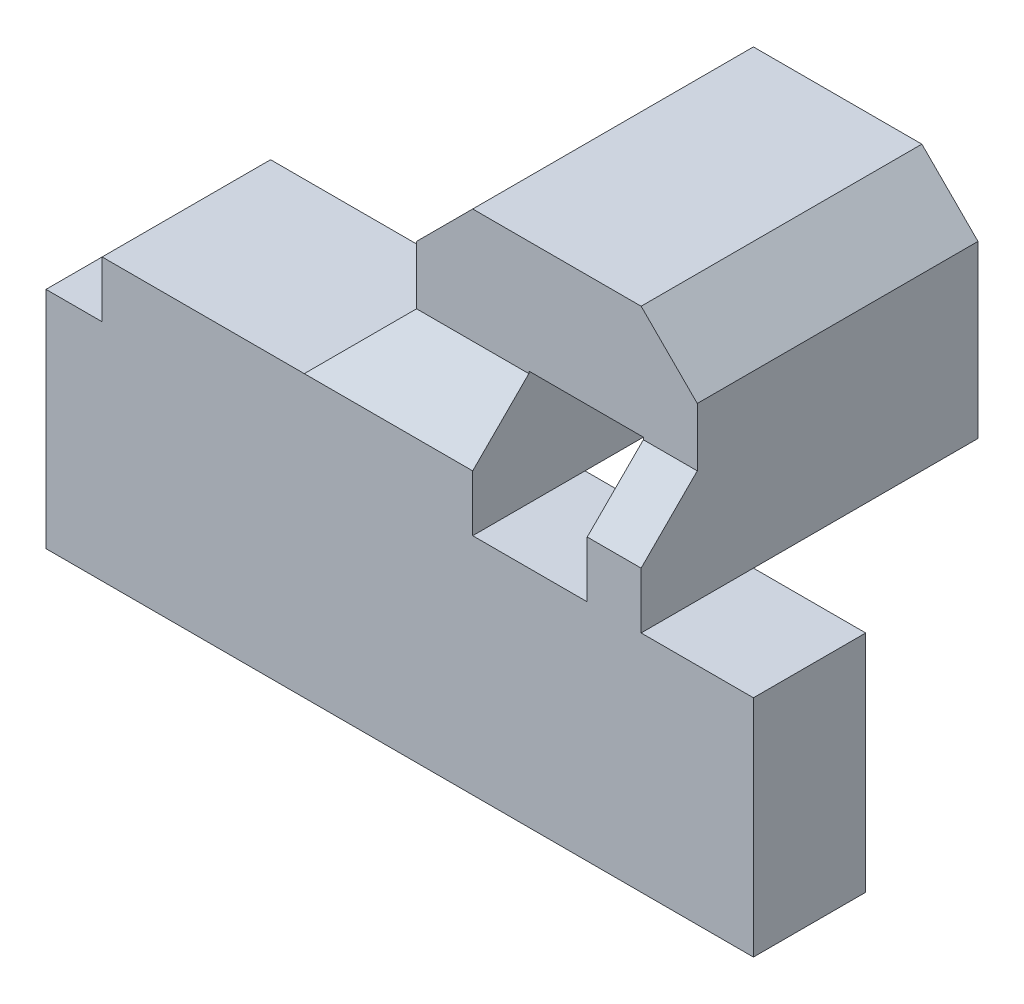
SolidWorks part; units mm, degrees
material "ABS"
ref_plane "Płaszczyzna przednia" through (0, 0, 0) normal (0, 0, 1) x (1, 0, 0)
ref_plane "Płaszczyzna górna" through (0, 0, 0) normal (0, 1, 0) x (1, 0, 0)
ref_plane "Płaszczyzna prawa" through (0, 0, 0) normal (1, 0, 0) x (0, 0, -1)
sketch "Szkic1" plane through (0, 0, 0) normal (0, 0, 1) x (1, 0, 0)
  line L1 (-29, -10) -> (29, -10)
  line L2 (-29, -10) -> (-29, 10)
  line L3 (-29, 10) -> (29, 10)
  line L4 (29, -10) -> (29, 10)
  line L5 (-29, -10) -> (29, 10) construction
  line L6 (-29, 10) -> (29, -10) construction
  point P0 (0, 0)
  dimension "D1" = 20
  dimension "D2" = 58
extrude "Dodanie-wyciągnięcie1" add sketch "Szkic1" along normal blind 5
sketch "Szkic2" plane through (29, 0, 0) normal (1, 0, 0) x (0, 0, -1)
  line L0 (0, 15) -> (-10, 15)
  line L1 (0, 10) -> (5, 10)
  line L2 (0, 10) -> (0, 15)
  line L3 (0, 15) -> (5, 15)
  line L4 (5, 10) -> (5, 15)
  line L5 (-5, 10) -> (0, 10)
  line L6 (-10, 15) -> (-10, 10)
  line L7 (-10, 10) -> (-5, 10)
  line M2 (0, 10) -> (-5, 10)
  dimension "D1" = 5
  dimension "D2" = 5
extrude "Dodanie-wyciągnięcie2" add sketch "Szkic2" against normal up to surface (58 mm away) contours L2 M2 | L1 L4 L3 L2 region at (29, 12.5, 5) region at (29, 12.5, -2.5) up to face at (-29, 0, 2.5)
sketch "Szkic3" plane through (0, -10, 0) normal (0, -1, 0) x (1, 0, 0)
  line L0 (-29, 0) -> (-34, 5)
  line L1 (-29, 5) -> (-29, 0) construction
  line L2 (-29, 0) -> (-34, 0) construction
  line L3 (-34, 5) -> (-34, 10)
  line L4 (-34, 10) -> (-29, 10)
  line L5 (-29, 10) -> (-24, 5)
  line L6 (-29, 5) -> (29, 5) construction
  line L7 (-29, 5) -> (29, 5)
  line L8 (-29, 5) -> (-29, 0)
  point P12 (0, 0)
  line M7 (29, 5) -> (-29, 5)
  line M8 (-29, 5) -> (-29, 0)
  dimension "D1" = 45
  dimension "D2" = 5
  dimension "D3" = 5
extrude "Dodanie-wyciągnięcie3" add sketch "Szkic3" against normal blind 20 contours L5 L4 L3 L0 M8 M7 region at (-30.25, -10, 6.25)
sketch "Szkic4" plane through (0, 0, 5) normal (0, 0, 1) x (1, 0, 0)
  line L1 (29, 10) -> (19, 10)
  line L2 (29, 10) -> (29, 15)
  line L3 (29, 15) -> (19, 15)
  line L4 (19, 10) -> (19, 15)
  line L6 (29, -10) -> (29, 10) construction
  line L7 (-29, 15) -> (29, 15) construction
  line L8 (29, 10) -> (-24, 10) construction
  point P4 (0, 0)
  point P8 (0, 0)
  dimension "D1" = 5
  dimension "D2" = 10
extrude "Wytnij-wyciągnięcie1" cut sketch "Szkic4" against normal through all and the other way through all
sketch "Szkic5" plane through (0, 0, 5) normal (0, 0, 1) x (1, 0, 0)
  line L0 (-34, 10) -> (-34, -10) construction
  line L1 (14.2, 10) -> (4, 10)
  line L2 (14.2, 10) -> (14.2, 20.2)
  line L3 (14.2, 20.2) -> (4, 20.2)
  line L4 (4, 10) -> (4, 20.2)
  line L5 (14.2, 10) -> (4, 20.2) construction
  line L6 (14.2, 20.2) -> (4, 10) construction
  line L7 (19, 10) -> (-24, 10) construction
  line L9 (29, 10) -> (19, 10) construction
  line L10 (-6, 10) -> (19, 10)
  line L11 (-6, 10) -> (-6, 30.2)
  line L12 (-6, 30.2) -> (19, 30.2)
  line L13 (19, 10) -> (19, 30.2)
  point P0 (9.1, 15.1)
  point P9 (0, 0)
  point P13 (0, 0)
  point P14 (0, 0)
  dimension "D1" = 10.2
  dimension "D2" = 38
  dimension "D3" = 10
  dimension "D4" = 10
  dimension "D5" = 4.8
extrude "Dodanie-wyciągnięcie4" add sketch "Szkic5" against normal blind 10 contours L13 L12 L11 L4 L3 L2 region at (5.8254, 21.3974, 5)
extrude "Wytnij-wyciągnięcie2" cut sketch "Szkic5<3>" against normal through all and the other way through all contours L4 L2 L3 region at (9.1, 15.1, 5)
sketch "Szkic5<3>" plane through (0, 0, 5) normal (0, 0, 1) x (1, 0, 0) same geometry as "Szkic5"
sketch "Szkic6" plane through (0, 10, 0) normal (0, 1, 0) x (1, 0, 0)
  line L1 (-29, -10) -> (29, -10)
  line L2 (-29, -10) -> (-29, -5)
  line L3 (-29, -5) -> (29, -5)
  line L4 (29, -10) -> (29, -5)
  dimension "D1" = 5
  dimension "D2" = 58
extrude "Dodanie-wyciągnięcie5" add sketch "Szkic6" against normal blind 20
sketch "Szkic7" plane through (0, -10, 0) normal (0, -1, 0) x (1, 0, 0)
  line L0 (-34, 10) -> (29, 10) construction
  line L1 (-34, 5) -> (-34, 10) construction
  circle A0 centre (-19, 5) radius 2
  circle A1 centre (11, 5) radius 2
  point P4 (0, 0)
  point P5 (0, 0)
  dimension "D1" = 4
  dimension "D2" = 5
  dimension "D3" = 15
  dimension "D4" = 30
extrude "Wytnij-wyciągnięcie3" cut sketch "Szkic7" against normal blind 10
sketch "Szkic10" plane through (0, 0, -5) normal (0, 0, -1) x (-1, 0, 0)
  line L0 (6, 15) -> (6, 10)
  line L10 (-4, 20.2) -> (-4, 10)
  line L11 (-4, 10) -> (29, 10)
  line L12 (29, 10) -> (29, 15)
  line L13 (29, 15) -> (6, 15)
  line L14 (6, 15) -> (6, 30.2)
  line L15 (6, 30.2) -> (-19, 30.2)
  line L16 (-19, 30.2) -> (-19, 10)
  line L17 (-19, 10) -> (-14.2, 10)
  line L18 (-14.2, 10) -> (-14.2, 20.2)
  line L19 (-14.2, 20.2) -> (-4, 20.2)
  line L20 (-4, 20.2) -> (-4, 10)
  line L21 (-4, 10) -> (29, 10)
  line L22 (29, 10) -> (29, 15)
  line L23 (29, 15) -> (6, 15)
  line L24 (6, 15) -> (6, 30.2)
  line L25 (6, 30.2) -> (-19, 30.2)
  line L26 (-19, 30.2) -> (-19, 10)
  line L27 (-19, 10) -> (-14.2, 10)
  line L28 (-14.2, 10) -> (-14.2, 20.2)
  line L29 (-14.2, 20.2) -> (-4, 20.2)
  line M11 (-4, 20.2) -> (-4, 10)
  line M12 (-4, 10) -> (29, 10)
  line M15 (6, 15) -> (6, 30.2)
  line M16 (6, 30.2) -> (-19, 30.2)
  line M17 (-19, 30.2) -> (-19, 10)
  line M18 (-19, 10) -> (-14.2, 10)
  line M19 (-14.2, 10) -> (-14.2, 20.2)
  line M20 (-14.2, 20.2) -> (-4, 20.2)
  dimension "D1" = 0
extrude "Dodanie-wyciągnięcie8" add sketch "Szkic10" along normal blind 10 contours L0 M15 M16 M17 M18 M19 M20 M11 M12 region at (5.8254, 21.3974, -5)
sketch "Szkic11" plane through (0, 0, -15) normal (0, 0, -1) x (-1, 0, 0)
  line L0 (-14.2, 10) -> (-4, 10)
  line L8 (6, 10) -> (6, 30.2)
  line L9 (6, 30.2) -> (-19, 30.2)
  line L10 (-19, 30.2) -> (-19, 10)
  line L11 (-19, 10) -> (-14.2, 10)
  line L12 (-14.2, 10) -> (-14.2, 20.2)
  line L13 (-14.2, 20.2) -> (-4, 20.2)
  line L14 (-4, 20.2) -> (-4, 10)
  line L15 (-4, 10) -> (6, 10)
  line L16 (6, 10) -> (6, 30.2)
  line L17 (6, 30.2) -> (-19, 30.2)
  line L18 (-19, 30.2) -> (-19, 10)
  line L19 (-19, 10) -> (-14.2, 10)
  line L20 (-14.2, 10) -> (-14.2, 20.2)
  line L21 (-14.2, 20.2) -> (-4, 20.2)
  line L22 (-4, 20.2) -> (-4, 10)
  line L23 (-4, 10) -> (6, 10)
  line M9 (6, 10) -> (6, 30.2)
  line M10 (6, 30.2) -> (-19, 30.2)
  line M11 (-19, 30.2) -> (-19, 10)
  line M12 (-19, 10) -> (-14.2, 10)
  line M13 (-14.2, 10) -> (-14.2, 20.2)
  line M14 (-14.2, 20.2) -> (-4, 20.2)
  line M15 (-4, 20.2) -> (-4, 10)
  line M16 (-4, 10) -> (6, 10)
  dimension "D1" = 0
extrude "Dodanie-wyciągnięcie9" add sketch "Szkic11" along normal blind 5 contours M16 M9 M10 M11 M12 M13 M14 M15 | L0 M13 M15 M14 region at (9.1, 15.1, -15) region at (5.8254, 21.3974, -15)
chamfer "Sfazowanie2" distance 5 angle 45 2 edges at (19, 30.2, -7.5) (-6, 30.2, -7.5)
chamfer "Sfazowanie3" distance 5 angle 45 2 edges at (-6, 15, 0) (-1, 15, 5)
